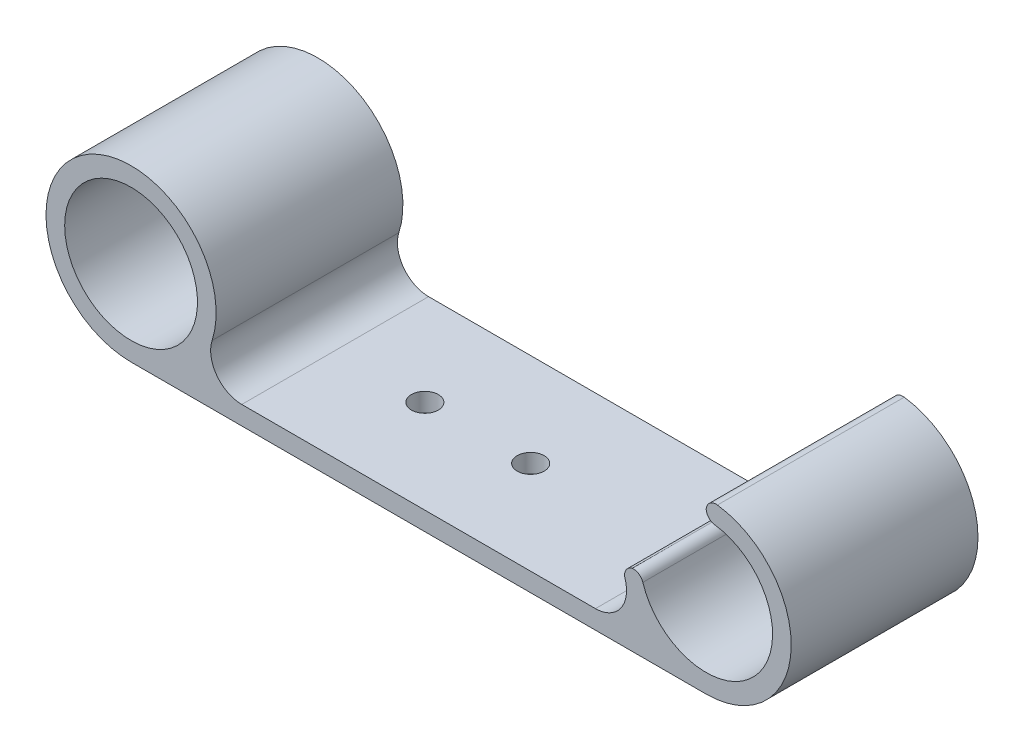
SolidWorks part; units mm, degrees
ref_plane "Front Plane" through (0, 0, 0) normal (0, 0, 1) x (1, 0, 0)
ref_plane "Top Plane" through (0, 0, 0) normal (0, 1, 0) x (1, 0, 0)
ref_plane "Right Plane" through (0, 0, 0) normal (1, 0, 0) x (0, 0, -1)
sketch "Sketch3" plane through (0, 0, 0) normal (0, 1, 0) x (1, 0, 0)
  line L1 (-57.15, -19.05) -> (57.15, -19.05)
  line L2 (-57.15, -19.05) -> (-57.15, 19.05)
  line L3 (-57.15, 19.05) -> (57.15, 19.05)
  line L4 (57.15, -19.05) -> (57.15, 19.05)
  line L5 (-57.15, -19.05) -> (57.15, 19.05) construction
  line L6 (-57.15, 19.05) -> (57.15, -19.05) construction
  point P0 (0, 0)
  dimension "D1" = 38.1
  dimension "D2" = 114.3
extrude "Boss-Extrude1" add sketch "Sketch3" along normal blind 3.81
sketch "Sketch4" plane through (0, 0, 0) normal (0, 0, 1) x (1, 0, 0)
  line L0 (-58.6588, 17.3553) -> (58.6588, 17.3553) construction
  line L1 (57.15, 3.81) -> (-57.15, 3.81) construction
  line L2 (0, -2.0955) -> (0, 2.0955) construction
  line L5 (20.955, 0) -> (-20.955, 0) construction
  line L8 (-57.15, 3.81) -> (57.15, 3.81) construction
  line L9 (-36.0719, 3.81) -> (36.0719, 3.81)
  line L11 (-57.15, 0) -> (57.15, 0) construction
  line L12 (74.7593, 0) -> (-74.7593, 0) construction
  line L13 (0, 3.81) -> (0, 0)
  line L14 (58.6588, 0) -> (-58.6588, 0)
  line L16 (58.6588, 17.3553) -> (41.5671, 14.3416) construction
  line L17 (58.6588, 17.3553) -> (58.6588, 34.7106) construction
  line L18 (58.6588, 17.3553) -> (64.5947, 33.664) construction
  line L19 (41.5671, 14.3416) -> (45.3193, 15.0032)
  line L20 (58.6588, 34.7106) -> (58.6588, 30.9006)
  circle A0 centre (-58.6588, 17.3553) radius 13.5453
  arc A1 (45.3193, 15.0032) -> (63.2916, 30.0837) centre (58.6588, 17.3553) ccw
  arc A2 (-42.1223, 12.0874) -> (-76.0141, 17.3553) centre (-58.6588, 17.3553) ccw
  arc A3 (42.1223, 12.0874) -> (41.5671, 14.3416) centre (58.6588, 17.3553) cw
  arc A4 (-36.0719, 3.81) -> (-42.1223, 12.0874) centre (-36.0719, 10.16) cw
  arc A5 (36.0719, 3.81) -> (42.1223, 12.0874) centre (36.0719, 10.16) ccw
  arc A6 (42.1223, 12.0874) -> (41.5671, 14.3416) centre (58.6588, 17.3553) cw
  arc A7 (-42.1223, 12.0874) -> (-76.0141, 17.3553) centre (-58.6588, 17.3553) ccw
  arc A8 (41.5671, 14.3416) -> (42.1223, 12.0874) centre (58.6588, 17.3553) ccw
  arc A9 (64.5947, 33.664) -> (76.0141, 17.3553) centre (58.6588, 17.3553) cw
  arc A10 (64.5947, 33.664) -> (76.0141, 17.3553) centre (58.6588, 17.3553) cw
  arc A11 (58.6588, 0) -> (64.5947, 33.664) centre (58.6588, 17.3553) ccw
  arc A12 (63.2916, 30.0837) -> (58.6588, 30.9006) centre (58.6588, 17.3553) ccw
  arc A13 (64.5947, 33.664) -> (58.6588, 34.7106) centre (58.6588, 17.3553) ccw
  arc A15 (-76.0141, 17.3553) -> (-58.6588, 0) centre (-58.6588, 17.3553) ccw
  point P6 (0, 17.3553)
  point P28 (-47.8084, 3.81)
  dimension "D1" = 27.0906
  dimension "D4" = 3.81
  dimension "D5" = 6.35
  dimension "D2" = 117.3176
  dimension "D6" = 100
  dimension "D7" = 20
sketch "Sketch5" plane through (0, 3.81, 0) normal (0, 1, 0) x (1, 0, 0)
  line L0 (0, -2.0955) -> (0, 2.0955) construction
  line L1 (57.15, 19.05) -> (-57.15, 19.05) construction
  line L2 (0, 13.545) -> (0, 19.05) construction
  line L3 (-2.0955, 0) -> (2.0955, 0) construction
  line L4 (0, -13.545) -> (0, -19.05) construction
  line L5 (-17.78, 19.05) -> (-17.78, -19.05) construction
  line L6 (-57.15, -19.05) -> (57.15, -19.05) construction
  circle A0 centre (0, 10.795) radius 2.75 construction
  circle A1 centre (0, -10.795) radius 2.75 construction
  circle A2 centre (-17.78, 10.795) radius 2.75 construction
  circle A3 centre (-17.78, -10.795) radius 2.75 construction
  circle A4 centre (-17.78, 0) radius 2.75
  circle A5 centre (3.81, 0) radius 2.75
  dimension "D2" = 5.5
  dimension "D1" = 21.59
  dimension "D3" = 17.78
  dimension "D4" = 21.59
extrude "Boss-Extrude2" add sketch "Sketch4" along normal mid plane 38.1 contours A0 A2 L12 L13 L9 A4 | A5 L9 L13 L12 A6 A1 A3 region at (-18.0359, 2.9744, 0) region at (46.8476, 8.7031, 0)
fillet "Fillet1" radius 2.032 4 edges at (58.6588, 34.7106, 0) (58.6588, 30.9006, 0) (45.3193, 15.0032, 0) (41.5671, 14.3416, 0)
extrude "Cut-Extrude4" cut sketch "Sketch5" against normal blind 12.7
